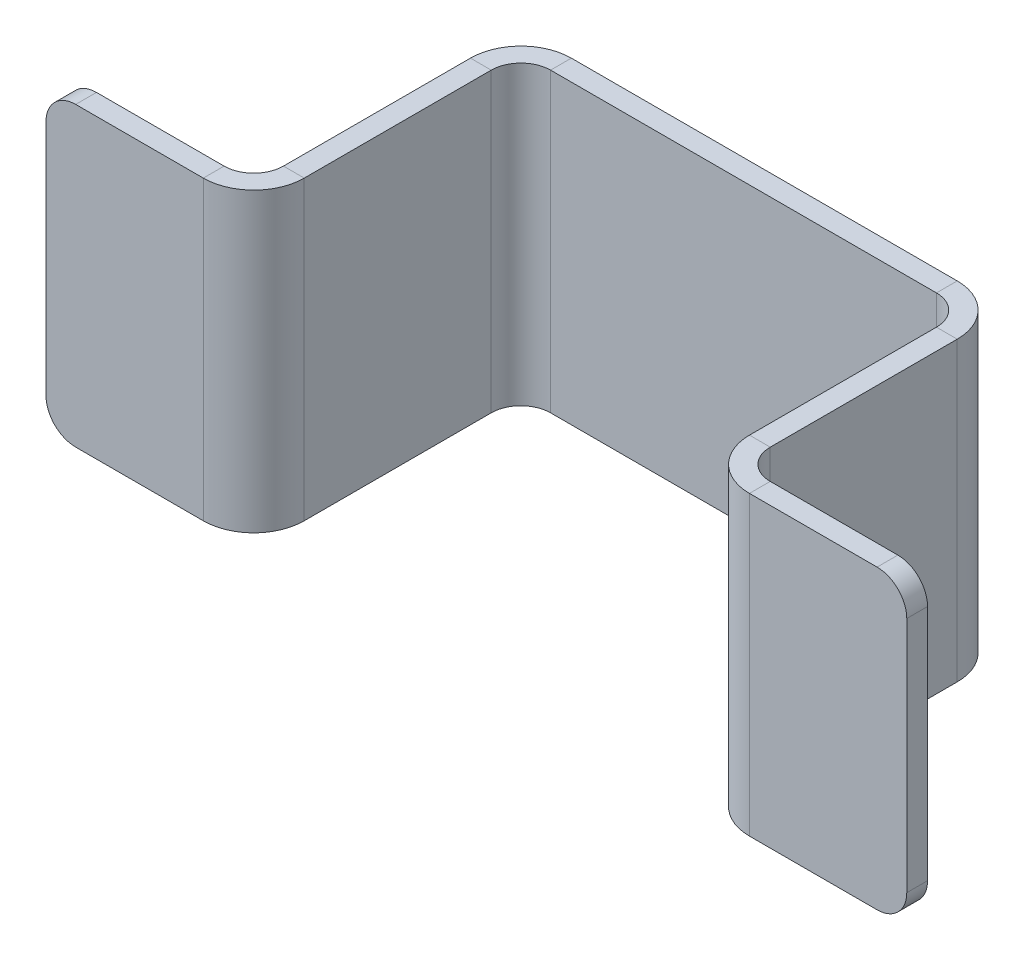
SolidWorks part; units mm, degrees
note: The reader was unsure of these and kept them because the rebuilt part matched: flange length of "Edge-Flange1", "Edge-Flange2", "Edge-Flange3", "Edge-Flange4".
material "1060 Alloy"
ref_plane "Front Plane" through (0, 0, 0) normal (0, 0, 1) x (1, 0, 0)
ref_plane "Top Plane" through (0, 0, 0) normal (0, 1, 0) x (1, 0, 0)
ref_plane "Right Plane" through (0, 0, 0) normal (1, 0, 0) x (0, 0, -1)
sketch "Sketch2" plane through (0, 0, 0) normal (0, 0, 1) x (1, 0, 0)
  line L1 (-7.5, 5) -> (7.5, 5)
  line L2 (-7.5, 5) -> (-7.5, -5)
  line L3 (-7.5, -5) -> (7.5, -5)
  line L4 (7.5, 5) -> (7.5, -5)
  line L5 (-7.5, 5) -> (7.5, -5) construction
  line L6 (-7.5, -5) -> (7.5, 5) construction
  point P0 (0, 0)
  dimension "D1" = 15
  dimension "D2" = 10
base flange "Base-Flange1" sketch "Sketch2" thickness 0.7 reverse thickness direction no parameters "D1"=1
edge flange "Edge-Flange1" sketch "Sketch9" flange angle 90 flange length 9 flange position material outside bend radius 1 thickness 0.7 relief rectangular parameters "D6"=10
sketch "Sketch9" plane through (-7.5, 0, 0) normal (-1, 0, 0) x (0, -1, 0)
  line L0 (-5, 0) -> (5, 0) construction
  line L1 (-5, 0) -> (5, 0)
  line L2 (-5, 0) -> (-5, 8.3)
  line L3 (-5, 8.3) -> (5, 8.3)
  line L4 (5, 8.3) -> (5, 0)
bend "EdgeBend1" bend radius 1 bend angle 90 parameters "D5"=1
edge flange "Edge-Flange2" sketch "Sketch12" flange angle 90 flange length 9 flange position material outside bend radius 1 thickness 0.7 relief rectangular parameters "D6"=10
sketch "Sketch12" plane through (7.5, 0, 0) normal (1, 0, 0) x (0, 1, 0)
  line L0 (-5, 0) -> (5, 0) construction
  line L1 (-5, 0) -> (5, 0)
  line L2 (-5, 0) -> (-5, 8.3)
  line L3 (-5, 8.3) -> (5, 8.3)
  line L4 (5, 8.3) -> (5, 0)
bend "EdgeBend2" bend radius 1 bend angle 90 parameters "D5"=2
edge flange "Edge-Flange3" sketch "Sketch15" flange angle 90 flange length 7 flange position material outside bend radius 1 thickness 0.7 relief rectangular parameters "D6"=10
sketch "Sketch15" plane through (8.2, 0, 8.3) normal (0, 0, 1) x (0, -1, 0)
  line L0 (-5, 0) -> (5, 0) construction
  line L1 (-5, 0) -> (5, 0)
  line L2 (-5, 0) -> (-5, 6.3)
  line L3 (-5, 6.3) -> (5, 6.3)
  line L4 (5, 6.3) -> (5, 0)
bend "EdgeBend3" bend radius 1 bend angle 90 parameters "D5"=3
edge flange "Edge-Flange4" sketch "Sketch18" flange angle 90 flange length 7 flange position material outside bend radius 1 thickness 0.7 relief rectangular parameters "D6"=10
sketch "Sketch18" plane through (-8.2, 0, 8.3) normal (0, 0, 1) x (0, 1, 0)
  line L0 (-5, 0) -> (5, 0) construction
  line L1 (-5, 0) -> (5, 0)
  line L2 (-5, 0) -> (-5, 6.3)
  line L3 (-5, 6.3) -> (5, 6.3)
  line L4 (5, 6.3) -> (5, 0)
bend "EdgeBend4" bend radius 1 bend angle 90 parameters "D5"=4
fillet "Fillet1" radius 1 4 edges at (-14.5, -5, 8.65) (-14.5, 5, 8.65) (14.5, -5, 8.65) (14.5, 5, 8.65)
sketch "Bend-Lines1" [suppressed] plane through (0, 0, 0) normal (0, 1, 0) x (1, 0, 0)
sketch "Bounding-Box1" [suppressed] plane through (0, 0, 0) normal (0, 1, 0) x (1, 0, 0)
sheet metal parameters "Sheet-Metal1" thickness 0.7 parameters "D1"=1
flat pattern "Flat-Pattern1" [suppressed]
sketch "Bend-Lines2" plane through (0, 0, 0) normal (0, 1, 0) x (1, 0, 0)
sketch3d "Bounding-Box2" [suppressed]
  line L0 (19.5, -5, 0) -> (-19.5, -5, 0) construction
  line L1 (19.5, 5, 0) -> (-19.5, 5, 0) construction
  line L2 (19.5, -5, 0) -> (19.5, 5, 0) construction
  line L3 (-19.5, -5, 0) -> (-19.5, 5, 0) construction
sheet metal parameters "Sheet-Metal2" thickness 0.7 parameters "D1"=1
flat pattern "Flat-Pattern1"
sketch "Bend-Lines2" plane through (0, 0, 0) normal (0, 0, 1) x (1, 0, 0)
  line L0 (-19.5603, 5) -> (-19.5603, -5) construction
  line L1 (-19.5603, 5) -> (-19.5603, -5) construction
sketch3d "Bounding-Box2" [suppressed]
  line L0 (-25.9206, -5, 0) -> (19.5, -5, 0) construction
  line L1 (-25.9206, 5, 0) -> (19.5, 5, 0) construction
  line L2 (-25.9206, -5, 0) -> (-25.9206, 5, 0) construction
  line L3 (19.5, -5, 0) -> (19.5, 5, 0) construction
bend of the flat pattern "Flatten-<EdgeBend1>1"
sheet metal parameters "Sheet-Metal3" thickness 0.7 parameters "D1"=1
flat pattern "Flat-Pattern1"
sketch "Bend-Lines2" plane through (0, 0, 0) normal (0, 0, 1) x (1, 0, 0)
  line L0 (-7.5603, 5) -> (-7.5603, -5) construction
  line L1 (-7.5603, 5) -> (-7.5603, -5) construction
  line L2 (7.5603, -5) -> (7.5603, 5) construction
  line L3 (7.5603, -5) -> (7.5603, 5) construction
sketch3d "Bounding-Box2" [suppressed]
  line L0 (-15.9206, -5, 0) -> (15.9206, -5, 0) construction
  line L1 (-15.9206, 5, 0) -> (15.9206, 5, 0) construction
  line L2 (-15.9206, -5, 0) -> (-15.9206, 5, 0) construction
  line L3 (15.9206, -5, 0) -> (15.9206, 5, 0) construction
bend of the flat pattern "Flatten-<EdgeBend1>1"
bend of the flat pattern "Flatten-<EdgeBend2>1"
sheet metal parameters "Sheet-Metal6" thickness 0.7 parameters "D1"=1
flat pattern "Flat-Pattern1"
sketch "Bend-Lines2" plane through (0, 0, 0) normal (0, 0, 1) x (1, 0, 0)
  line L0 (-7.5603, 5) -> (-7.5603, -5) construction
  line L1 (-7.5603, 5) -> (-7.5603, -5) construction
  line L2 (7.5603, -5) -> (7.5603, 5) construction
  line L3 (7.5603, -5) -> (7.5603, 5) construction
  line L4 (15.9809, -5) -> (15.9809, 5) construction
  line L5 (15.9809, -5) -> (15.9809, 5) construction
sketch3d "Bounding-Box2" [suppressed]
  line L0 (-15.9206, -5, 0) -> (22.3412, -5, 0) construction
  line L1 (-15.9206, 5, 0) -> (22.3412, 5, 0) construction
  line L2 (-15.9206, -5, 0) -> (-15.9206, 5, 0) construction
  line L3 (22.3412, -5, 0) -> (22.3412, 5, 0) construction
bend of the flat pattern "Flatten-<EdgeBend1>1"
bend of the flat pattern "Flatten-<EdgeBend2>1"
bend of the flat pattern "Flatten-<EdgeBend3>1"
sheet metal parameters "Sheet-Metal7" thickness 0.7 parameters "D1"=1
flat pattern "Flat-Pattern1"
sketch "Bend-Lines2" plane through (0, 0, 0) normal (0, 0, 1) x (1, 0, 0)
  line L0 (-7.5603, 5) -> (-7.5603, -5) construction
  line L1 (-7.5603, 5) -> (-7.5603, -5) construction
  line L2 (7.5603, -5) -> (7.5603, 5) construction
  line L3 (7.5603, -5) -> (7.5603, 5) construction
  line L4 (15.9809, -5) -> (15.9809, 5) construction
  line L5 (15.9809, -5) -> (15.9809, 5) construction
  line L6 (-15.9809, 5) -> (-15.9809, -5) construction
  line L7 (-15.9809, 5) -> (-15.9809, -5) construction
sketch3d "Bounding-Box2" [suppressed]
  line L0 (-22.3412, -5, 0) -> (22.3412, -5, 0) construction
  line L1 (-22.3412, 5, 0) -> (22.3412, 5, 0) construction
  line L2 (-22.3412, -5, 0) -> (-22.3412, 5, 0) construction
  line L3 (22.3412, -5, 0) -> (22.3412, 5, 0) construction
bend of the flat pattern "Flatten-<EdgeBend1>1"
bend of the flat pattern "Flatten-<EdgeBend2>1"
bend of the flat pattern "Flatten-<EdgeBend3>1"
bend of the flat pattern "Flatten-<EdgeBend4>1"
